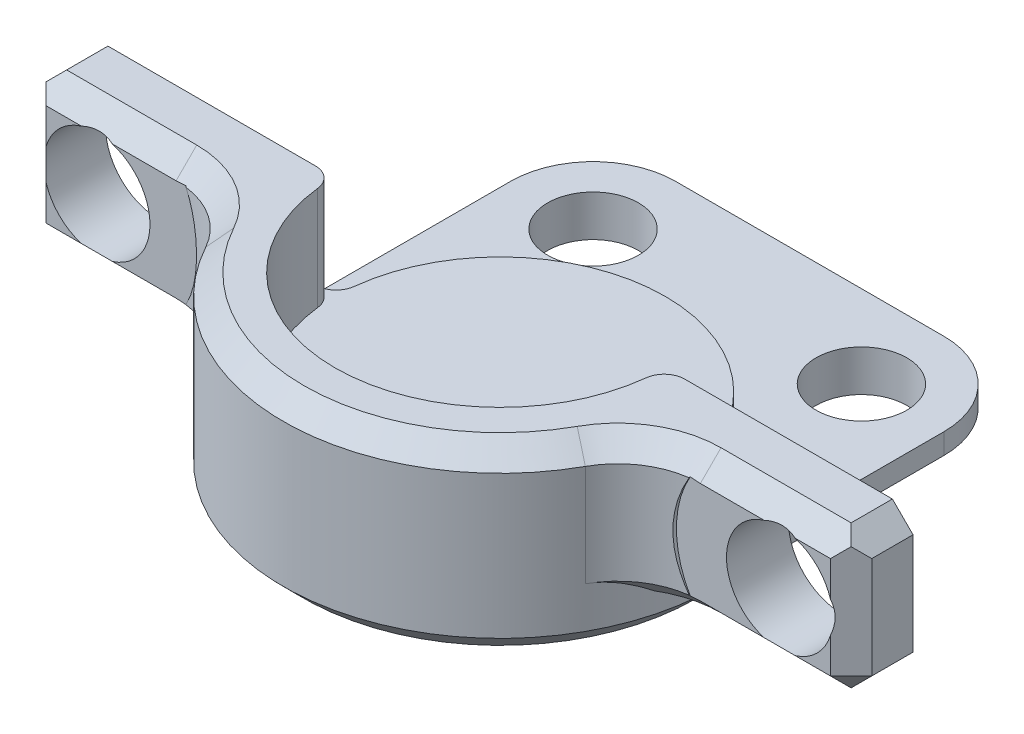
SolidWorks part; units mm, degrees
material "6061 合金"
ref_plane "前视基准面" through (0, 0, 0) normal (0, 0, 1) x (1, 0, 0)
ref_plane "上视基准面" through (0, 0, 0) normal (0, 1, 0) x (1, 0, 0)
ref_plane "右视基准面" through (0, 0, 0) normal (1, 0, 0) x (0, 0, -1)
sketch "草图1" plane through (0, 0, 0) normal (0, 0, 1) x (1, 0, 0)
  line L1 (-20, 4.35) -> (20, 4.35)
  line L2 (-20, 4.35) -> (-20, -2.575)
  line L3 (-20, -2.575) -> (20, -2.575)
  line L4 (20, 4.35) -> (20, -2.575)
  point P4 (0, 0)
extrude "凸台-拉伸1" add sketch "草图1" along normal blind 10.5
sketch "草图2" plane through (0, -2.575, 0) normal (0, -1, 0) x (1, 0, 0)
  circle A0 centre (0, 0) radius 8 construction
  circle A1 centre (0, 0) radius 8
extrude "切除-拉伸1" cut sketch "草图2" against normal blind 10.5
sketch "草图3" plane through (0, -2.575, 0) normal (0, -1, 0) x (1, 0, 0)
  line L1 (-20, 0) -> (-20, 3)
  line L2 (20, 3) -> (13.075, 3)
  line L3 (20, 3) -> (10.0623, 3)
  line L4 (-20, 10.5) -> (-20, 0) construction
  line L5 (20, 0) -> (20, 3)
  line L6 (20, 10.5) -> (20, 0) construction
  line L7 (-10.0623, 3) -> (-20, 3)
  line L8 (-20, 0) -> (-22, 0)
  line L9 (-22, 0) -> (-22, 12)
  line L10 (20, 0) -> (22, 0)
  line L11 (22, 0) -> (22, 12)
  line L12 (22, 12) -> (-22, 12)
  arc A0 (10.0623, 3) -> (-10.0623, 3) centre (0, 0) ccw
  dimension "D1" = 3
extrude "切除-拉伸2" cut sketch "草图3" against normal blind 10.5
fillet "圆角2" radius 4 2 edges at (10.0623, 0.8875, 3) (-10.0623, 0.8875, 3)
sketch "草图5" plane through (0, 0, 3) normal (0, 0, 1) x (1, 0, 0)
  circle A0 centre (16.5375, 0.8875) radius 2.575
  circle A1 centre (-16.5375, 0.8875) radius 2.575
extrude "切除-拉伸3" cut sketch "草图5" against normal blind 10.5
sketch "草图7" plane through (0, -0.65, 0) normal (0, -1, 0) x (1, 0, 0)
  circle A0 centre (0, 0) radius 8
extrude "凸台-拉伸2" add sketch "草图7" along normal up to surface (1.925 mm away)
fillet "圆角3" radius 1 2 edges at (8, -1.6125, 0) (-8, -1.6125, 0)
sketch "草图8" plane through (0, -2.575, 0) normal (0, -1, 0) x (1, 0, 0)
  line L0 (-10.5, 0) -> (-10.5, -15)
  line L1 (-10.5, -15) -> (10.5, -15)
  line L2 (10.5, -15) -> (10.5, 0)
  arc A0 (10.5, 0) -> (-10.5, 0) centre (0, 0) ccw
extrude "凸台-拉伸3" add sketch "草图8" along normal blind 2
fillet "圆角4" radius 4 2 edges at (10.5, -3.575, -15) (-10.5, -3.575, -15)
sketch "草图10" plane through (0, -4.575, 0) normal (0, -1, 0) x (1, 0, 0)
  circle A0 centre (-6.5, -11) radius 2.2
  circle A1 centre (6.5, -11) radius 2.2
extrude "切除-拉伸5" cut sketch "草图10" against normal blind 2
chamfer "倒角2" distance 1 angle 45 19 edges at (20, 0.8875, 3) (-20, 0.8875, 3) (20, -2.575, 1.5) (-20, -2.575, 1.5) (-16.3492, 4.35, 3) (16.3492, 4.35, 3) (-10.6642, 4.35, 3.5559) (10.6642, 4.35, 3.5559) (0, 4.35, 10.5) (0, -4.575, -15) (9.3284, -4.575, -13.8284) (-9.3284, -4.575, -13.8284) (10.5, -4.575, -5.5) (-10.5, -4.575, -5.5) (0, -4.575, 10.5) (10.6642, -2.575, 3.5559) (16.3492, -2.575, 3) (-10.6642, -2.575, 3.5559) (-16.3492, -2.575, 3)
fillet "圆角5" radius 1 2 edges at (8, 1.85, 0) (-8, 1.85, 0)
sketch "草图11" plane through (0, 0, 3) normal (0, 0, 1) x (1, 0, 0)
  circle A0 centre (16.5375, 0.8875) radius 5
  circle A1 centre (-16.5375, 0.8875) radius 5
extrude "切除-拉伸6" cut sketch "草图11" along normal blind 19
chamfer "倒角3" distance 1 angle 45 2 edges at (20, 4.35, 1) (-20, 4.35, 1)
